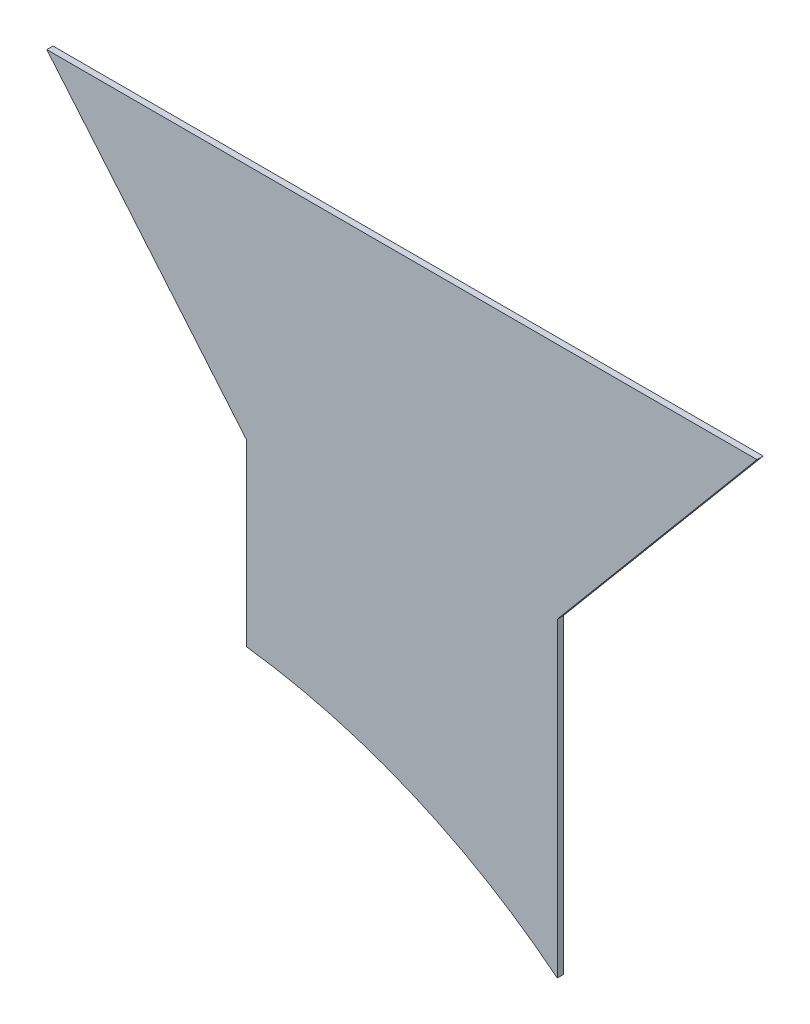
SolidWorks part; units mm, degrees
material "201 Annealed Stainless Steel (SS)"
ref_plane "Front Plane" through (0, 0, 0) normal (0, 0, 1) x (1, 0, 0)
ref_plane "Top Plane" through (0, 0, 0) normal (0, 1, 0) x (1, 0, 0)
ref_plane "Right Plane" through (0, 0, 0) normal (1, 0, 0) x (0, 0, -1)
sketch "Sketch1" plane through (0, 0, 0) normal (0, 0, 1) x (1, 0, 0)
  line L1 (38.1, 0) -> (38.1, 76.2)
  line L2 (38.1, 76.2) -> (87.0804, 134.5726)
  line L6 (0, 0) -> (38.1, 0) construction
  line L7 (0, 0) -> (0, 134.5726) construction
  line L8 (-87.0804, 134.5726) -> (87.0804, 134.5726)
  line L9 (-38.1, 32.2375) -> (-38.1, 76.2)
  line L10 (-38.1, 76.2) -> (-87.0804, 134.5726)
  line L11 (0, 0) -> (0, -123.071) construction
  line L12 (-57.15, -118.9672) -> (24.7773, -118.9672) construction
  line L13 (-38.1, 0) -> (-38.1, 32.2375) construction
  line L14 (-38.1, 0) -> (0, 0) construction
  line L15 (-38.1, 32.2375) -> (-38.1, -118.9672) construction
  line L16 (38.1, 0) -> (38.1, -109.3889) construction
  arc A1 (38.1, 0) -> (-38.1, 32.2375) centre (-57.15, -118.9672) ccw
  circle A2 centre (-57.15, -118.9672) radius 152.4 construction
  point P4 (-38.1, -122.9868)
  point P16 (38.1, -109.3889)
  point P18 (30.0273, -123.071)
  dimension "D5" = 152.4
  dimension "D6" = 95.25
  dimension "D1" = 38.1
  dimension "D2" = 140
  dimension "D3" = 76.2
  dimension "D4" = 76.2
extrude "Funnel - Side Panel" add sketch "Sketch1" along normal blind 1.5189
